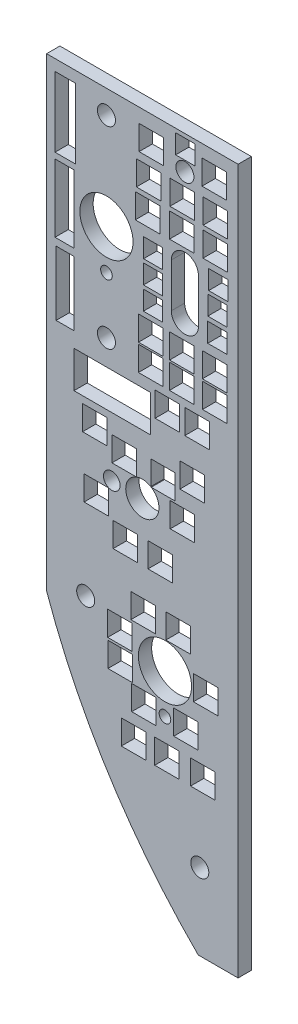
SolidWorks part; units mm, degrees
material "Acrylic (Medium-high impact)"
ref_plane "Front Plane" through (0, 0, 0) normal (0, 0, 1) x (1, 0, 0)
ref_plane "Top Plane" through (0, 0, 0) normal (0, 1, 0) x (1, 0, 0)
ref_plane "Right Plane" through (0, 0, 0) normal (1, 0, 0) x (0, 0, -1)
sketch "Sketch1" plane through (0, 0, 0) normal (0, 0, 1) x (1, 0, 0)
  line L4 (-45.72, 26.9875) -> (-45.72, -84.1375)
  line L5 (-9.525, -141.2875) -> (0, -141.2875)
  line L6 (0, -141.2875) -> (0, 26.9875)
  line L7 (0, 26.9875) -> (-45.72, 26.9875)
  line L8 (-45.72, 26.9875) -> (-45.72, -84.1375)
  line L9 (-9.525, -141.2875) -> (0, -141.2875)
  line L10 (0, -141.2875) -> (0, 26.9875)
  line L11 (0, 26.9875) -> (-45.72, 26.9875)
  arc A1 (-45.72, -84.1375) -> (-9.525, -141.2875) centre (97.9169, -33.2042) ccw
  arc A2 (-45.72, -84.1375) -> (-9.525, -141.2875) centre (97.9169, -33.2042) ccw
  dimension "D1" = 0
extrude "Boss-Extrude1" add sketch "Sketch1" against normal blind 3.175
hole_wizard "1/2 (0.5) Diameter Hole1" positions "Sketch4" profile "Sketch3" hole size "1/2" standard "ANSI Inch" end condition through all
sketch "Sketch4" plane through (0, 0, 0) normal (0, 0, 1) x (1, 0, 0)
  point P0 (-17.4625, -86.5505)
  point P4 (-31.4325, -1.6203)
sketch "Sketch3" plane through (-17.4625, -86.5505, 0) normal (1, 0, 0) x (0, -1, 0)
  line L0 (0, 0) -> (0, 3.175)
  line L1 (0, 3.175) -> (6.35, 3.175)
  line L2 (6.35, 3.175) -> (6.35, 0)
  line L5 (6.35, 0) -> (0, 0)
  line L11 (0, -6.35) -> (0, 107.95) construction
  dimension "Thru Hole Dia." = 12.7
  dimension "Thru Hole Depth" = 3.175
hole_wizard "5/16 (0.3125) Diameter Hole1" positions "Sketch6" profile "Sketch5" hole size "5/16" standard "ANSI Inch" end condition through all
sketch "Sketch6" plane through (0, 0, 0) normal (0, 0, 1) x (1, 0, 0)
  point P0 (-22.86, -53.5305)
sketch "Sketch5" plane through (-22.86, -53.5305, 0) normal (1, 0, 0) x (0, -1, 0)
  line L0 (0, 0) -> (0, 3.175)
  line L1 (0, 3.175) -> (3.9687, 3.175)
  line L2 (3.9687, 3.175) -> (3.9687, 0)
  line L5 (3.9687, 0) -> (0, 0)
  line L11 (0, -6.35) -> (0, 107.95) construction
  dimension "Thru Hole Dia." = 7.9375
  dimension "Thru Hole Depth" = 3.175
hole_wizard "5/32 (0.15625) Diameter Hole1" positions "Sketch8" profile "Sketch7" hole size "5/32" standard "ANSI Inch" end condition through all
sketch "Sketch8" plane through (0, 0, 0) normal (0, 0, 1) x (1, 0, 0)
  line L0 (-22.86, -49.5617) -> (-22.86, -53.5305) construction
  circle A0 centre (-22.86, -53.5305) radius 3.9688 construction
  point P11 (-30.1611, -53.5305)
sketch "Sketch7" plane through (-30.1611, -53.5305, 0) normal (1, 0, 0) x (0, -1, 0)
  line L0 (0, 0) -> (0, 3.175)
  line L1 (0, 3.175) -> (1.9844, 3.175)
  line L2 (1.9844, 3.175) -> (1.9844, 0)
  line L5 (1.9844, 0) -> (0, 0)
  line L11 (0, -6.35) -> (0, 107.95) construction
  dimension "Thru Hole Dia." = 3.9688
  dimension "Thru Hole Depth" = 3.175
hole_wizard "7/64 (0.10938) Diameter Hole1" positions "Sketch10" profile "Sketch9" hole size "7/64" standard "ANSI Inch" end condition through all
sketch "Sketch10" plane through (0, 0, 0) normal (0, 0, 1) x (1, 0, 0)
  point P0 (-17.4646, -95.9667)
  point P3 (-31.4325, -11.1589)
sketch "Sketch9" plane through (-17.4646, -95.9667, 0) normal (1, 0, 0) x (0, -1, 0)
  line L0 (0, 0) -> (0, 3.175)
  line L1 (0, 3.175) -> (1.3891, 3.175)
  line L2 (1.3891, 3.175) -> (1.3891, 0)
  line L5 (1.3891, 0) -> (0, 0)
  line L11 (0, -6.35) -> (0, 107.95) construction
  dimension "Thru Hole Dia." = 2.7783
  dimension "Thru Hole Depth" = 3.175
sketch "Sketch11" plane through (0, 0, -3.175) normal (0, 0, -1) x (-1, 0, 0)
  line L5 (19.8437, -15.24) -> (19.8437, 3.175)
  line L6 (19.8437, 3.175) -> (8.7312, 3.175)
  line L7 (8.7312, 3.175) -> (8.7312, -15.24)
  line L8 (8.7312, -15.24) -> (19.8437, -15.24)
  line L9 (19.8437, -15.24) -> (19.8437, 3.175)
  line L10 (19.8437, 3.175) -> (8.7312, 3.175)
  line L11 (8.7312, 3.175) -> (8.7312, -15.24)
  line L12 (8.7312, -15.24) -> (19.8437, -15.24)
  dimension "D1" = 0
extrude "Cut-Extrude4" [suppressed] cut sketch "Sketch11" against normal through all
hole_wizard "#6 Clearance Hole1" positions "Sketch13" profile "Sketch12" hole size "#6" standard "ANSI Inch" end condition through all
sketch "Sketch13" plane through (0, 0, -3.175) normal (0, 0, -1) x (-1, 0, 0)
  point P0 (12.7, 19.05)
  point P3 (36.3855, -80.4545)
  point P6 (9.144, -122.9995)
  point P10 (31.4325, -24.62)
  point P13 (31.4325, 21.4048)
sketch "Sketch12" plane through (-12.7, 19.05, -3.175) normal (1, 0, 0) x (0, 1, 0)
  line L0 (0, 0) -> (0, 3.175)
  line L1 (0, 3.175) -> (2.1526, 3.175)
  line L2 (2.1526, 3.175) -> (2.1526, 0)
  line L5 (2.1526, 0) -> (0, 0)
  line L11 (0, -6.35) -> (0, 107.95) construction
  dimension "Thru Hole Dia." = 4.3053
  dimension "Thru Hole Depth" = 3.175
hole_wizard "#16 (0.177) Diameter Hole1" positions "Sketch15" profile "Sketch14" hole size "#16" standard "ANSI Inch" end condition through all
sketch "Sketch15" plane through (0, 0, -3.175) normal (0, 0, -1) x (-1, 0, 0)
  line L5 (12.7, 2.794) -> (12.7, -14.859) construction
  line L6 (12.7, -6.0325) -> (17.8753, -6.0325) construction
  point P26 (12.7, -0.7804)
  point P33 (12.7, -11.2846)
sketch "Sketch14" plane through (-12.7, -11.2846, -3.175) normal (1, 0, 0) x (0, 1, 0)
  line L0 (0, 0) -> (0, 3.175)
  line L1 (0, 3.175) -> (2.2479, 3.175)
  line L2 (2.2479, 3.175) -> (2.2479, 0)
  line L5 (2.2479, 0) -> (0, 0)
  line L11 (0, -6.35) -> (0, 107.95) construction
  dimension "Thru Hole Dia." = 4.4958
  dimension "Thru Hole Depth" = 3.175
sketch "Sketch16" plane through (0, 0, -4.775) normal (0, 0, -1) x (-1, 0, 0)
  line L0 (12.7, -11.2846) -> (12.7, -0.7804) construction
  line L1 (2.6659, -22.1354) -> (8.5079, -22.1354)
  line L2 (2.6659, -22.1354) -> (2.6659, -27.9774)
  line L3 (2.6659, -27.9774) -> (8.5079, -27.9774)
  line L4 (8.5079, -22.1354) -> (8.5079, -27.9774)
  line L5 (2.6659, -22.1354) -> (8.5079, -27.9774) construction
  line L6 (2.6659, -27.9774) -> (8.5079, -22.1354) construction
  line L7 (10.5519, -22.1354) -> (16.3939, -22.1354)
  line L8 (10.5519, -22.1354) -> (10.5519, -27.9774)
  line L9 (10.5519, -27.9774) -> (16.3939, -27.9774)
  line L10 (16.3939, -22.1354) -> (16.3939, -27.9774)
  line L11 (10.5519, -22.1354) -> (16.3939, -27.9774) construction
  line L12 (10.5519, -27.9774) -> (16.3939, -22.1354) construction
  line L13 (17.9569, -22.1354) -> (23.7989, -22.1354)
  line L14 (17.9569, -22.1354) -> (17.9569, -27.9774)
  line L15 (17.9569, -27.9774) -> (23.7989, -27.9774)
  line L16 (23.7989, -22.1354) -> (23.7989, -27.9774)
  line L17 (17.9569, -22.1354) -> (23.7989, -27.9774) construction
  line L18 (17.9569, -27.9774) -> (23.7989, -22.1354) construction
  line L19 (17.9319, -15.8614) -> (23.7739, -15.8614)
  line L20 (17.9319, -15.8614) -> (17.9319, -21.7034)
  line L21 (17.9319, -21.7034) -> (23.7739, -21.7034)
  line L22 (23.7739, -15.8614) -> (23.7739, -21.7034)
  line L23 (17.9319, -15.8614) -> (23.7739, -21.7034) construction
  line L24 (17.9319, -21.7034) -> (23.7739, -15.8614) construction
  line L25 (10.5149, -15.8364) -> (16.3569, -15.8364)
  line L26 (10.5149, -15.8364) -> (10.5149, -21.6784)
  line L27 (10.5149, -21.6784) -> (16.3569, -21.6784)
  line L28 (16.3569, -15.8364) -> (16.3569, -21.6784)
  line L29 (10.5149, -15.8364) -> (16.3569, -21.6784) construction
  line L30 (10.5149, -21.6784) -> (16.3569, -15.8364) construction
  line L31 (2.6919, -15.8114) -> (8.5339, -15.8114)
  line L32 (2.6919, -15.8114) -> (2.6919, -21.6534)
  line L33 (2.6919, -21.6534) -> (8.5339, -21.6534)
  line L34 (8.5339, -15.8114) -> (8.5339, -21.6534)
  line L35 (2.6919, -15.8114) -> (8.5339, -21.6534) construction
  line L36 (2.6919, -21.6534) -> (8.5339, -15.8114) construction
  line L41 (39.2165, -27.0307) -> (43.4505, -27.0307)
  line L42 (39.2165, -27.0307) -> (39.2165, -11.6644)
  line L47 (39.2165, -11.6644) -> (43.4505, -11.6644)
  line L48 (43.4505, -27.0307) -> (43.4505, -11.6644)
  line L53 (39.2165, 6.231) -> (43.7187, 6.231)
  line L54 (39.2165, 6.231) -> (39.2165, -9.9754)
  line L55 (39.2165, -9.9754) -> (43.7187, -9.9754)
  line L56 (43.7187, 6.231) -> (43.7187, -9.9754)
  line L57 (38.8582, 7.6135) -> (43.7187, 7.6135)
  line L58 (38.8582, 7.6135) -> (38.8582, 24.3196)
  line L59 (38.8582, 24.3196) -> (43.7187, 24.3196)
  line L60 (43.7187, 7.6135) -> (43.7187, 24.3196)
  line L61 (12.7249, -29.6544) -> (6.8829, -29.6544)
  line L62 (12.7249, -29.6544) -> (12.7249, -35.4964)
  line L63 (12.7249, -35.4964) -> (6.8829, -35.4964)
  line L64 (6.8829, -29.6544) -> (6.8829, -35.4964)
  line L65 (12.7249, -29.6544) -> (6.8829, -35.4964) construction
  line L66 (12.7249, -35.4964) -> (6.8829, -29.6544) construction
  line L67 (19.8109, -29.6034) -> (13.9689, -29.6034)
  line L68 (19.8109, -29.6034) -> (19.8109, -35.4454)
  line L69 (19.8109, -35.4454) -> (13.9689, -35.4454)
  line L70 (13.9689, -29.6034) -> (13.9689, -35.4454)
  line L71 (19.8109, -29.6034) -> (13.9689, -35.4454) construction
  line L72 (19.8109, -35.4454) -> (13.9689, -29.6034) construction
  line L73 (5.5089, -101.4346) -> (11.3509, -101.4346)
  line L74 (5.5089, -101.4346) -> (5.5089, -107.2766)
  line L75 (5.5089, -107.2766) -> (11.3509, -107.2766)
  line L76 (11.3509, -101.4346) -> (11.3509, -107.2766)
  line L77 (5.5089, -101.4346) -> (11.3509, -107.2766) construction
  line L78 (5.5089, -107.2766) -> (11.3509, -101.4346) construction
  line L79 (14.0689, -101.4088) -> (19.9109, -101.4088)
  line L80 (14.0689, -101.4088) -> (14.0689, -107.2508)
  line L81 (14.0689, -107.2508) -> (19.9109, -107.2508)
  line L82 (19.9109, -101.4088) -> (19.9109, -107.2508)
  line L83 (14.0689, -101.4088) -> (19.9109, -107.2508) construction
  line L84 (14.0689, -107.2508) -> (19.9109, -101.4088) construction
  line L85 (22.0469, -101.4342) -> (27.8889, -101.4342)
  line L86 (22.0469, -101.4342) -> (22.0469, -107.2762)
  line L87 (22.0469, -107.2762) -> (27.8889, -107.2762)
  line L88 (27.8889, -101.4342) -> (27.8889, -107.2762)
  line L89 (22.0469, -101.4342) -> (27.8889, -107.2762) construction
  line L90 (22.0469, -107.2762) -> (27.8889, -101.4342) construction
  line L91 (9.5239, -93.1288) -> (15.3659, -93.1288)
  line L92 (9.5239, -93.1288) -> (9.5239, -98.9708)
  line L93 (9.5239, -98.9708) -> (15.3659, -98.9708)
  line L94 (15.3659, -93.1288) -> (15.3659, -98.9708)
  line L95 (9.5239, -93.1288) -> (15.3659, -98.9708) construction
  line L96 (9.5239, -98.9708) -> (15.3659, -93.1288) construction
  line L97 (19.5569, -93.0776) -> (25.3989, -93.0776)
  line L98 (19.5569, -93.0776) -> (19.5569, -98.9196)
  line L99 (19.5569, -98.9196) -> (25.3989, -98.9196)
  line L100 (25.3989, -93.0776) -> (25.3989, -98.9196)
  line L101 (19.5569, -93.0776) -> (25.3989, -98.9196) construction
  line L102 (19.5569, -98.9196) -> (25.3989, -93.0776) construction
  line L103 (4.8249, -83.6546) -> (10.6669, -83.6546)
  line L104 (4.8249, -83.6546) -> (4.8249, -89.4966)
  line L105 (4.8249, -89.4966) -> (10.6669, -89.4966)
  line L106 (10.6669, -83.6546) -> (10.6669, -89.4966)
  line L107 (4.8249, -83.6546) -> (10.6669, -89.4966) construction
  line L108 (4.8249, -89.4966) -> (10.6669, -83.6546) construction
  line L109 (25.2329, -86.9818) -> (31.0749, -86.9818)
  line L110 (25.2329, -86.9818) -> (25.2329, -92.8238)
  line L111 (25.2329, -92.8238) -> (31.0749, -92.8238)
  line L112 (31.0749, -86.9818) -> (31.0749, -92.8238)
  line L113 (25.2329, -86.9818) -> (31.0749, -92.8238) construction
  line L114 (25.2329, -92.8238) -> (31.0749, -86.9818) construction
  line L115 (25.2959, -80.5808) -> (31.1379, -80.5808)
  line L116 (25.2959, -80.5808) -> (25.2959, -86.4228)
  line L117 (25.2959, -86.4228) -> (31.1379, -86.4228)
  line L118 (31.1379, -80.5808) -> (31.1379, -86.4228)
  line L119 (25.2959, -80.5808) -> (31.1379, -86.4228) construction
  line L120 (25.2959, -86.4228) -> (31.1379, -80.5808) construction
  line L121 (19.7609, -74.1546) -> (25.6029, -74.1546)
  line L122 (19.7609, -74.1546) -> (19.7609, -79.9966)
  line L123 (19.7609, -79.9966) -> (25.6029, -79.9966)
  line L124 (25.6029, -74.1546) -> (25.6029, -79.9966)
  line L125 (19.7609, -74.1546) -> (25.6029, -79.9966) construction
  line L126 (19.7609, -79.9966) -> (25.6029, -74.1546) construction
  line L127 (11.4019, -74.1804) -> (17.2439, -74.1804)
  line L128 (11.4019, -74.1804) -> (11.4019, -80.0224)
  line L129 (11.4019, -80.0224) -> (17.2439, -80.0224)
  line L130 (17.2439, -74.1804) -> (17.2439, -80.0224)
  line L131 (11.4019, -74.1804) -> (17.2439, -80.0224) construction
  line L132 (11.4019, -80.0224) -> (17.2439, -74.1804) construction
  line L133 (15.6709, -61.6074) -> (21.5129, -61.6074)
  line L134 (15.6709, -61.6074) -> (15.6709, -67.4494)
  line L135 (15.6709, -67.4494) -> (21.5129, -67.4494)
  line L136 (21.5129, -61.6074) -> (21.5129, -67.4494)
  line L137 (15.6709, -61.6074) -> (21.5129, -67.4494) construction
  line L138 (15.6709, -67.4494) -> (21.5129, -61.6074) construction
  line L139 (24.0019, -61.582) -> (29.8439, -61.582)
  line L140 (24.0019, -61.582) -> (24.0019, -67.424)
  line L141 (24.0019, -67.424) -> (29.8439, -67.424)
  line L142 (29.8439, -61.582) -> (29.8439, -67.424)
  line L143 (24.0019, -61.582) -> (29.8439, -67.424) construction
  line L144 (24.0019, -67.424) -> (29.8439, -61.582) construction
  line L145 (30.9369, -55.4098) -> (36.7789, -55.4098)
  line L146 (30.9369, -55.4098) -> (30.9369, -61.2518)
  line L147 (30.9369, -61.2518) -> (36.7789, -61.2518)
  line L148 (36.7789, -55.4098) -> (36.7789, -61.2518)
  line L149 (30.9369, -55.4098) -> (36.7789, -61.2518) construction
  line L150 (30.9369, -61.2518) -> (36.7789, -55.4098) construction
  line L151 (10.3599, -50.66) -> (16.2019, -50.66)
  line L152 (10.3599, -50.66) -> (10.3599, -56.502)
  line L153 (10.3599, -56.502) -> (16.2019, -56.502)
  line L154 (16.2019, -50.66) -> (16.2019, -56.502)
  line L155 (10.3599, -50.66) -> (16.2019, -56.502) construction
  line L156 (10.3599, -56.502) -> (16.2019, -50.66) construction
  line L157 (8.0509, -41.2874) -> (13.8929, -41.2874)
  line L158 (8.0509, -41.2874) -> (8.0509, -47.1294)
  line L159 (8.0509, -47.1294) -> (13.8929, -47.1294)
  line L160 (13.8929, -41.2874) -> (13.8929, -47.1294)
  line L161 (8.0509, -41.2874) -> (13.8929, -47.1294) construction
  line L162 (8.0509, -47.1294) -> (13.8929, -41.2874) construction
  line L163 (15.0109, -44.3354) -> (20.8529, -44.3354)
  line L164 (15.0109, -44.3354) -> (15.0109, -50.1774)
  line L165 (15.0109, -50.1774) -> (20.8529, -50.1774)
  line L166 (20.8529, -44.3354) -> (20.8529, -50.1774)
  line L167 (15.0109, -44.3354) -> (20.8529, -50.1774) construction
  line L168 (15.0109, -50.1774) -> (20.8529, -44.3354) construction
  line L169 (24.2819, -43.9798) -> (30.1239, -43.9798)
  line L170 (24.2819, -43.9798) -> (24.2819, -49.8218)
  line L171 (24.2819, -49.8218) -> (30.1239, -49.8218)
  line L172 (30.1239, -43.9798) -> (30.1239, -49.8218)
  line L173 (24.2819, -43.9798) -> (30.1239, -49.8218) construction
  line L174 (24.2819, -49.8218) -> (30.1239, -43.9798) construction
  line L175 (31.2919, -41.0588) -> (37.1339, -41.0588)
  line L176 (31.2919, -41.0588) -> (31.2919, -46.9008)
  line L177 (31.2919, -46.9008) -> (37.1339, -46.9008)
  line L178 (37.1339, -41.0588) -> (37.1339, -46.9008)
  line L179 (31.2919, -41.0588) -> (37.1339, -46.9008) construction
  line L180 (31.2919, -46.9008) -> (37.1339, -41.0588) construction
  line L185 (9.4609, -11.2846) -> (9.4609, -0.7804)
  line L186 (15.9391, -11.2846) -> (15.9391, -0.7804)
  line L191 (39.1895, -30.6633) -> (20.8742, -30.6633)
  line L192 (39.1895, -30.6633) -> (39.1895, -39.4353)
  line L193 (2.6809, -9.0944) -> (7.2529, -9.0944)
  line L194 (2.6809, -9.0944) -> (2.6809, -13.6664)
  line L195 (2.6809, -13.6664) -> (7.2529, -13.6664)
  line L196 (7.2529, -9.0944) -> (7.2529, -13.6664)
  line L197 (2.6809, -9.0944) -> (7.2529, -13.6664) construction
  line L198 (2.6809, -13.6664) -> (7.2529, -9.0944) construction
  line L199 (2.6659, -3.4664) -> (7.2379, -3.4664)
  line L200 (2.6659, -3.4664) -> (2.6659, -8.0384)
  line L201 (2.6659, -8.0384) -> (7.2379, -8.0384)
  line L202 (7.2379, -3.4664) -> (7.2379, -8.0384)
  line L203 (2.6659, -3.4664) -> (7.2379, -8.0384) construction
  line L204 (2.6659, -8.0384) -> (7.2379, -3.4664) construction
  line L205 (2.4609, 1.9176) -> (7.0329, 1.9176)
  line L206 (2.4609, 1.9176) -> (2.4609, -2.6544)
  line L207 (2.4609, -2.6544) -> (7.0329, -2.6544)
  line L208 (7.0329, 1.9176) -> (7.0329, -2.6544)
  line L209 (2.4609, 1.9176) -> (7.0329, -2.6544) construction
  line L210 (2.4609, -2.6544) -> (7.0329, 1.9176) construction
  line L211 (2.5389, 9.2076) -> (8.3809, 9.2076)
  line L212 (2.5389, 9.2076) -> (2.5389, 3.3656)
  line L213 (2.5389, 3.3656) -> (8.3809, 3.3656)
  line L214 (8.3809, 9.2076) -> (8.3809, 3.3656)
  line L215 (2.5389, 9.2076) -> (8.3809, 3.3656) construction
  line L216 (2.5389, 3.3656) -> (8.3809, 9.2076) construction
  line L217 (10.5379, 9.1566) -> (16.3799, 9.1566)
  line L218 (10.5379, 9.1566) -> (10.5379, 3.3146)
  line L219 (10.5379, 3.3146) -> (16.3799, 3.3146)
  line L220 (16.3799, 9.1566) -> (16.3799, 3.3146)
  line L221 (10.5379, 9.1566) -> (16.3799, 3.3146) construction
  line L222 (10.5379, 3.3146) -> (16.3799, 9.1566) construction
  line L223 (18.7049, 9.0556) -> (24.5469, 9.0556)
  line L224 (18.7049, 9.0556) -> (18.7049, 3.2136)
  line L225 (18.7049, 3.2136) -> (24.5469, 3.2136)
  line L226 (24.5469, 9.0556) -> (24.5469, 3.2136)
  line L227 (18.7049, 9.0556) -> (24.5469, 3.2136) construction
  line L228 (18.7049, 3.2136) -> (24.5469, 9.0556) construction
  line L229 (17.9969, 0.7356) -> (22.5689, 0.7356)
  line L230 (17.9969, 0.7356) -> (17.9969, -3.8364)
  line L231 (17.9969, -3.8364) -> (22.5689, -3.8364)
  line L232 (22.5689, 0.7356) -> (22.5689, -3.8364)
  line L233 (17.9969, 0.7356) -> (22.5689, -3.8364) construction
  line L234 (17.9969, -3.8364) -> (22.5689, 0.7356) construction
  line L235 (18.0219, -4.6994) -> (22.5939, -4.6994)
  line L236 (18.0219, -4.6994) -> (18.0219, -9.2714)
  line L237 (18.0219, -9.2714) -> (22.5939, -9.2714)
  line L238 (22.5939, -4.6994) -> (22.5939, -9.2714)
  line L239 (18.0219, -4.6994) -> (22.5939, -9.2714) construction
  line L240 (18.0219, -9.2714) -> (22.5939, -4.6994) construction
  line L241 (18.0479, -10.1354) -> (22.6199, -10.1354)
  line L242 (18.0479, -10.1354) -> (18.0479, -14.7074)
  line L243 (18.0479, -14.7074) -> (22.6199, -14.7074)
  line L244 (22.6199, -10.1354) -> (22.6199, -14.7074)
  line L245 (18.0479, -10.1354) -> (22.6199, -14.7074) construction
  line L246 (18.0479, -14.7074) -> (22.6199, -10.1354) construction
  line L247 (2.4859, 16.0666) -> (8.3279, 16.0666)
  line L248 (2.4859, 16.0666) -> (2.4859, 10.2246)
  line L249 (2.4859, 10.2246) -> (8.3279, 10.2246)
  line L250 (8.3279, 16.0666) -> (8.3279, 10.2246)
  line L251 (2.4859, 16.0666) -> (8.3279, 10.2246) construction
  line L252 (2.4859, 10.2246) -> (8.3279, 16.0666) construction
  line L253 (10.4389, 15.9896) -> (16.2809, 15.9896)
  line L254 (10.4389, 15.9896) -> (10.4389, 10.1476)
  line L255 (10.4389, 10.1476) -> (16.2809, 10.1476)
  line L256 (16.2809, 15.9896) -> (16.2809, 10.1476)
  line L257 (10.4389, 15.9896) -> (16.2809, 10.1476) construction
  line L258 (10.4389, 10.1476) -> (16.2809, 15.9896) construction
  line L259 (18.4399, 15.9896) -> (24.2819, 15.9896)
  line L260 (18.4399, 15.9896) -> (18.4399, 10.1476)
  line L261 (18.4399, 10.1476) -> (24.2819, 10.1476)
  line L262 (24.2819, 15.9896) -> (24.2819, 10.1476)
  line L263 (18.4399, 15.9896) -> (24.2819, 10.1476) construction
  line L264 (18.4399, 10.1476) -> (24.2819, 15.9896) construction
  line L265 (17.8049, 23.6096) -> (23.6469, 23.6096)
  line L266 (17.8049, 23.6096) -> (17.8049, 17.7676)
  line L267 (17.8049, 17.7676) -> (23.6469, 17.7676)
  line L268 (23.6469, 23.6096) -> (23.6469, 17.7676)
  line L269 (17.8049, 23.6096) -> (23.6469, 17.7676) construction
  line L270 (17.8049, 17.7676) -> (23.6469, 23.6096) construction
  line L271 (2.7659, 23.9906) -> (8.6079, 23.9906)
  line L272 (2.7659, 23.9906) -> (2.7659, 18.1486)
  line L273 (2.7659, 18.1486) -> (8.6079, 18.1486)
  line L274 (8.6079, 23.9906) -> (8.6079, 18.1486)
  line L275 (2.7659, 23.9906) -> (8.6079, 18.1486) construction
  line L276 (2.7659, 18.1486) -> (8.6079, 23.9906) construction
  line L277 (10.3369, 26.0476) -> (14.9089, 26.0476)
  line L278 (10.3369, 26.0476) -> (10.3369, 21.4756)
  line L279 (10.3369, 21.4756) -> (14.9089, 21.4756)
  line L280 (14.9089, 26.0476) -> (14.9089, 21.4756)
  line L281 (10.3369, 26.0476) -> (14.9089, 21.4756) construction
  line L282 (10.3369, 21.4756) -> (14.9089, 26.0476) construction
  line L283 (39.1895, -39.4353) -> (20.8742, -39.4353)
  line L284 (20.8742, -30.6633) -> (20.8742, -39.4353)
  arc A0 (9.4609, -11.2846) -> (15.9391, -11.2846) centre (12.7, -11.2846) ccw
  arc A1 (15.9391, -0.7804) -> (9.4609, -0.7804) centre (12.7, -0.7804) ccw
  point P0 (5.5869, -25.0564)
  point P6 (13.4729, -25.0564)
  point P12 (20.8779, -25.0564)
  point P18 (20.8529, -18.7824)
  point P24 (13.4359, -18.7574)
  point P30 (5.6129, -18.7324)
  point P50 (9.8039, -32.5754)
  point P57 (16.8899, -32.5244)
  point P63 (8.4299, -104.3556)
  point P69 (0, 0)
  point P75 (24.9679, -104.3552)
  point P81 (12.4449, -96.0498)
  point P87 (22.4779, -95.9986)
  point P93 (7.7459, -86.5756)
  point P99 (28.1539, -89.9028)
  point P105 (28.2169, -83.5018)
  point P111 (22.6819, -77.0756)
  point P117 (14.3229, -77.1014)
  point P123 (18.5919, -64.5284)
  point P129 (26.9229, -64.503)
  point P135 (33.8579, -58.3308)
  point P141 (13.2809, -53.581)
  point P147 (10.9719, -44.2084)
  point P153 (17.9319, -47.2564)
  point P159 (27.2029, -46.9008)
  point P165 (34.2129, -43.9798)
  point P173 (12.7, -6.0325)
  point P179 (28.2324, -38.0057)
  point P180 (38.7981, -31.1808)
  point P181 (21.45, -39.1125)
  point P182 (0, 0)
  point P183 (4.9669, -11.3804)
  point P189 (4.9519, -5.7524)
  point P195 (4.7469, -0.3684)
  point P201 (5.4599, 6.2866)
  point P207 (13.4589, 6.2356)
  point P213 (21.6259, 6.1346)
  point P219 (20.2829, -1.5504)
  point P225 (20.3079, -6.9854)
  point P231 (20.3339, -12.4214)
  point P237 (5.4069, 13.1456)
  point P243 (13.3599, 13.0686)
  point P249 (21.3609, 13.0686)
  point P255 (20.7259, 20.6886)
  point P261 (5.6869, 21.0696)
  point P267 (12.6229, 23.7616)
  point P273 (0, 0)
  point P274 (0, 0)
  point P277 (0, 0)
  point P278 (0, 0)
  point P279 (0, 0)
  point P280 (0, 0)
  point P281 (0, 0)
  point P282 (0, 0)
  point P283 (0, 0)
  point P284 (0, 0)
  point P285 (0, 0)
  point P286 (0, 0)
  point P287 (0, 0)
  point P288 (0, 0)
  point P289 (0, 0)
  point P290 (0, 0)
  point P291 (0, 0)
  point P292 (0, 0)
  point P293 (0, 0)
  point P294 (0, 0)
  point P295 (0, 0)
  point P296 (0, 0)
  point P297 (0, 0)
  point P298 (0, 0)
  point P299 (0, 0)
  point P300 (0, 0)
  point P301 (0, 0)
  point P302 (0, 0)
  point P303 (0, 0)
  point P304 (0, 0)
  point P305 (0, 0)
  point P306 (0, 0)
  point P307 (0, 0)
  point P308 (0, 0)
  point P309 (0, 0)
  point P310 (0, 0)
  point P311 (0, 0)
  point P312 (0, 0)
  point P313 (0, 0)
  point P314 (0, 0)
  point P315 (0, 0)
  point P316 (0, 0)
  dimension "D1" = 5.842
  dimension "D2" = 5.842
  dimension "D3" = 4.572
extrude "Cut-Extrude5" cut sketch "Sketch16" against normal through all
